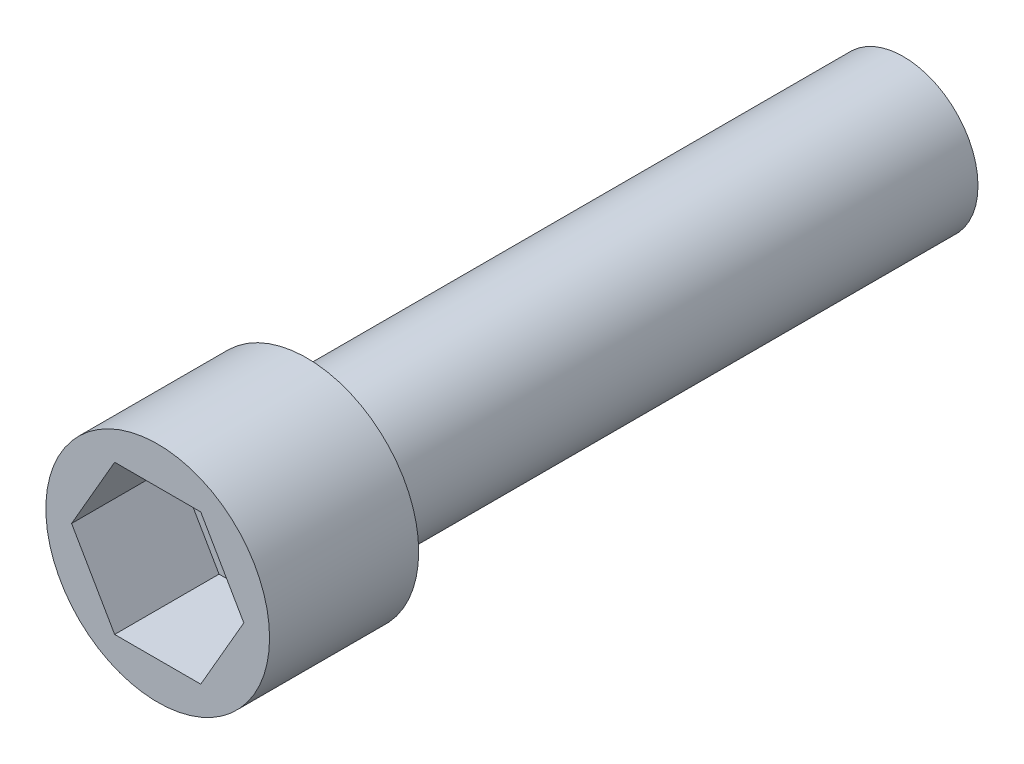
SolidWorks part; units mm, degrees
material "AISI 304"
ref_plane "Front Plane" through (0, 0, 0) normal (0, 0, 1) x (1, 0, 0)
ref_plane "Top Plane" through (0, 0, 0) normal (0, 1, 0) x (1, 0, 0)
ref_plane "Right Plane" through (0, 0, 0) normal (1, 0, 0) x (0, 0, -1)
sketch "Sketch1" plane through (0, 0, 0) normal (0, 0, 1) x (1, 0, 0)
  line L1 (5.7735, 0) -> (2.8868, 5)
  line L2 (2.8868, 5) -> (-2.8868, 5)
  line L3 (-2.8868, 5) -> (-5.7735, 0)
  line L4 (-5.7735, 0) -> (-2.8868, -5)
  line L5 (-2.8868, -5) -> (2.8868, -5)
  line L6 (2.8868, -5) -> (5.7735, 0)
  circle A0 centre (0, 0) radius 5
  circle A1 centre (0, 0) radius 7.5
  circle A2 centre (0, 0) radius 5 construction
  dimension "D2" = 15
  dimension "D3" = 10
  dimension "D1" = 10
extrude "Boss-Extrude1" add sketch "Sketch1" against normal blind 10 contours A1 L6 L5 L4 L3 L2 L1 | L2 L3 L4 L5 L6 L1 region at (-7.2879, 0, 0)
extrude "Boss-Extrude2" add sketch "Sketch1<4>" against normal blind 50 contours A0 region at (0, 0, 0)
sketch "Sketch1<4>" plane through (0, 0, 0) normal (0, 0, 1) x (1, 0, 0) same geometry as "Sketch1"
extrude "Cut-Extrude1" cut sketch "Sketch1<5>" against normal blind 7 and the other way through all contours L2 L3 L4 L5 L6 L1
sketch "Sketch1<5>" plane through (0, 0, 0) normal (0, 0, 1) x (1, 0, 0) same geometry as "Sketch1"
